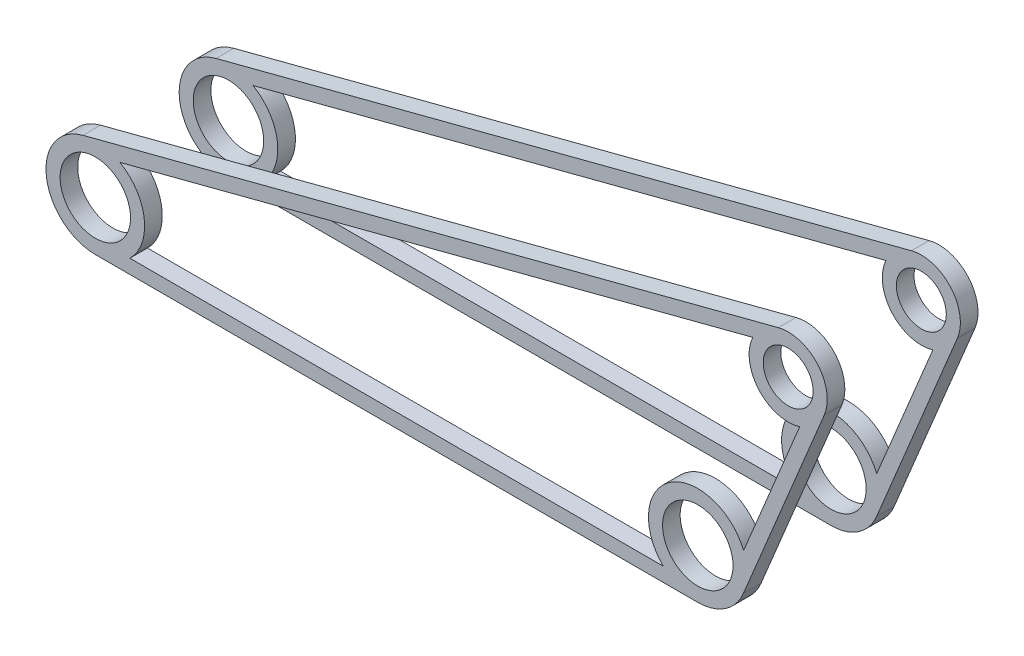
SolidWorks part; units mm, degrees
material "AISI 4130 Steel, annealed at 865C"
ref_plane "Front Plane" through (0, 0, 0) normal (0, 0, 1) x (1, 0, 0)
ref_plane "Top Plane" through (0, 0, 0) normal (0, 1, 0) x (1, 0, 0)
ref_plane "Right Plane" through (0, 0, 0) normal (1, 0, 0) x (0, 0, -1)
sketch "Sketch1" plane through (0, 0, 0) normal (0, 0, 1) x (1, 0, 0)
  line L0 (0, 0) -> (108.585, 0) construction
  line L1 (108.585, 0) -> (124.8778, 34.4406) construction
  line L2 (124.8778, 34.4406) -> (0, 0) construction
  line L3 (-2.2409, 8.6029) -> (123.1032, 41.2533)
  line L4 (131.3803, 31.7426) -> (116.7963, -3.407)
  line L5 (108.585, -8.89) -> (0, -8.89)
  line L6 (-1.6007, 6.1449) -> (123.7434, 38.7953)
  line L7 (0, -6.35) -> (108.585, -6.35)
  line L8 (114.4502, -2.4335) -> (129.0342, 32.7161)
  line L9 (111.596, -21.6868) -> (108.585, 0) construction
  circle A0 centre (0, 0) radius 6.35
  circle A1 centre (108.585, 0) radius 6.35
  circle A2 centre (124.8778, 34.4406) radius 4.5
  circle A3 centre (0, 0) radius 8.89
  circle A4 centre (108.585, 0) radius 8.89
  circle A5 centre (124.8778, 34.4406) radius 7.04
  dimension "D1" = 9
  dimension "D2" = 12.7
  dimension "D3" = 12.7
  dimension "D6" = 2.54
  dimension "D7" = 2.54
  dimension "D8" = 2.54
  dimension "D4" = 108.585
  dimension "D5" = 129.54
  dimension "D9" = 38.1
extrude "Boss-Extrude1" add sketch "Sketch1" along normal blind 3.175 from offset 10.4115 contours A5 L3 A3 L6 | L6 A3 L7 A0 | A4 L7 A3 L5 | L7 A4 L8 A1 | A5 L8 A4 L4 | A5 L6 A2 L8 | L7 A3 L6 A0 | L8 A4 L7 A1 | L6 A5 L8 A2 region at (1.146, 8.5805, 0) region at (60.9965, 23.7793, 0) region at (129.0654, 39.8588, 0) region at (54.2925, -7.6406, 0) region at (7.54, 4.3695, 0) region at (121.1641, 37.9583, 0) region at (105.2983, -8.0507, 0) region at (123.0705, 14.8619, 0) region at (103.7755, 7.2025, 0)
extrude "Boss-Extrude2" add sketch "Sketch1<4>" against normal blind 3.175 from offset 10.4115 separate body contours A5 L3 A3 L6 | L6 A3 L7 A0 | L7 A3 L6 A0 | A4 L7 A3 L5 | L7 A4 L8 A1 | L8 A4 L7 A1 | A5 L8 A4 L4 | L6 A5 L8 A2 | A5 L6 A2 L8 region at (1.146, 8.5805, 0) region at (60.9965, 23.7793, 0) region at (129.0654, 39.8588, 0) region at (54.2925, -7.6406, 0) region at (7.54, 4.3695, 0) region at (121.1641, 37.9583, 0) region at (105.2983, -8.0507, 0) region at (123.0705, 14.8619, 0) region at (103.7755, 7.2025, 0) offset against normal yes
sketch "Sketch1<4>" plane through (0, 0, 0) normal (0, 0, 1) x (1, 0, 0) same geometry as "Sketch1"
equation "\"D19@Boss-Extrude2\"=\"Gap\"/2"
equation "\"Gap\"= .8198"
equation "\"D19@Boss-Extrude1\"=\"Gap\"/2"
